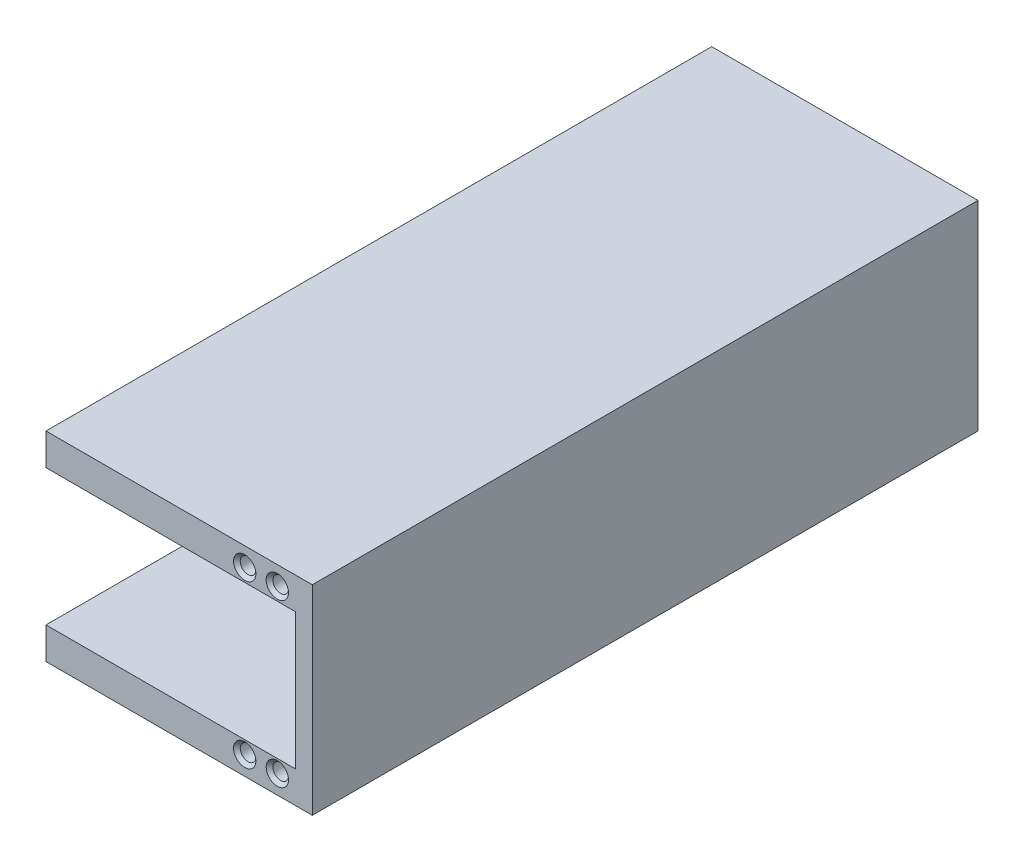
SolidWorks part; units mm, degrees
material "ABS"
ref_plane "Front Plane" through (0, 0, 0) normal (0, 0, 1) x (1, 0, 0)
ref_plane "Top Plane" through (0, 0, 0) normal (0, 1, 0) x (1, 0, 0)
ref_plane "Right Plane" through (0, 0, 0) normal (1, 0, 0) x (0, 0, -1)
sketch "Sketch1" plane through (0, 0, 0) normal (0, 0, 1) x (1, 0, 0)
  line L0 (-40, 30) -> (40, 30)
  line L1 (-40, 30) -> (40, 30) construction
  line L2 (-40, 30) -> (-40, -30) construction
  line L3 (-40, -30) -> (40, -30) construction
  line L4 (40, 30) -> (40, -30) construction
  line L5 (-40, 30) -> (40, -30) construction
  line L6 (-40, -30) -> (40, 30) construction
  line L7 (40, 30) -> (40, -30)
  line L8 (40, -30) -> (-40, -30)
  line L9 (-40, -30) -> (-40, -20.45)
  line L10 (-40, -20.45) -> (35, -20.45)
  line L11 (35, -20.45) -> (35, 20.45)
  line L12 (35, 20.45) -> (-40, 20.45)
  line L13 (-40, 20.45) -> (-40, 30)
  point P0 (0, 0)
  dimension "D1" = 60
  dimension "D2" = 80
  dimension "D3" = 40.9
  dimension "D5" = 5
extrude "Boss-Extrude1" add sketch "Sketch1" along normal blind 200
sketch "Sketch2" plane through (0, 0, 200) normal (0, 0, 1) x (1, 0, 0)
  line L0 (35, 20.45) -> (14.2, 20.45) construction
  line L1 (-40, 20.45) -> (35, 20.45) construction
  line L2 (24.6, 20.45) -> (24.6, 24.34) construction
  line L3 (24.6, 24.34) -> (29.5, 24.34) construction
  line L4 (35, 20.45) -> (35, -20.45) construction
  line L5 (35, 0) -> (40, 0) construction
  line L6 (40, -30) -> (40, 30) construction
  circle A0 centre (29.5, 24.34) radius 2.35
  circle A1 centre (19.7, 24.34) radius 2.35
  circle A2 centre (19.7, -24.34) radius 2.35
  circle A3 centre (29.5, -24.34) radius 2.35
  dimension "D4" = 4.7
  dimension "D1" = 20.8
  dimension "D2" = 3.89
  dimension "D3" = 4.9
extrude "Cut-Extrude1" cut sketch "Sketch2" against normal blind 8
sketch "Sketch3" plane through (0, 0, 0) normal (0, 0, -1) x (-1, 0, 0)
  line L0 (-35, 20.45) -> (-14.2, 20.45) construction
  line L1 (40, 20.45) -> (-35, 20.45) construction
  line L2 (-35, 20.45) -> (-35, -20.45) construction
  line L3 (-35, 0) -> (-40, 0) construction
  line L4 (-40, -30) -> (-40, 30) construction
  line L5 (-24.6, 20.45) -> (-24.6, 24.34) construction
  line L6 (-24.6, 24.34) -> (-29.5, 24.34) construction
  circle A0 centre (-29.5, 24.34) radius 2.35
  circle A1 centre (-19.7, 24.34) radius 2.35
  circle A2 centre (-19.7, -24.34) radius 2.35
  circle A3 centre (-29.5, -24.34) radius 2.35
  dimension "D4" = 4.7
  dimension "D1" = 20.8
  dimension "D2" = 3.89
  dimension "D3" = 4.9
extrude "Cut-Extrude2" cut sketch "Sketch3" against normal blind 8
chamfer "Chamfer1" distance 1 angle 45 8 edges at (17.35, -24.34, 0) (31.85, -24.34, 0) (27.15, 24.34, 0) (22.05, 24.34, 0) (27.15, -24.34, 200) (22.05, -24.34, 200) (17.35, 24.34, 200) (31.85, 24.34, 200)
